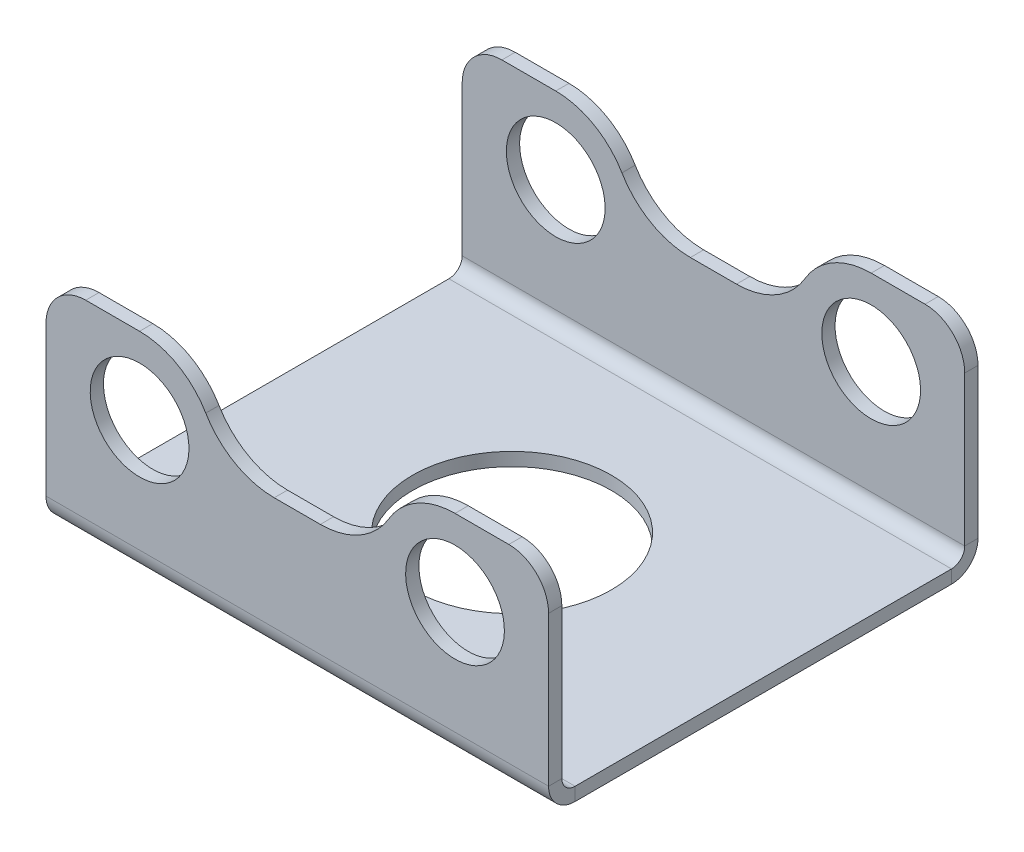
SolidWorks part; units mm, degrees
note: The reader was unsure of these and kept them because the rebuilt part matched: flange length of "Edge-Flange1".
material "Brass"
ref_plane "Front Plane" through (0, 0, 0) normal (0, 0, 1) x (1, 0, 0)
ref_plane "Top Plane" through (0, 0, 0) normal (0, 1, 0) x (1, 0, 0)
ref_plane "Right Plane" through (0, 0, 0) normal (1, 0, 0) x (0, 0, -1)
sketch "Sketch1" plane through (0, 0, 0) normal (0, 1, 0) x (1, 0, 0)
  line L0 (-24.0792, 18.034) -> (24.0792, 18.034)
  line L1 (24.0792, 18.034) -> (24.0792, -18.034)
  line L2 (24.0792, -18.034) -> (-24.0792, -18.034)
  line L3 (-24.0792, -18.034) -> (-24.0792, 18.034)
  line L4 (-24.0792, -18.034) -> (24.0792, 18.034) construction
  circle A0 centre (0, 0) radius 9.525
  point P5 (0, 0)
  dimension "D3" = 19.05
  dimension "D1" = 36.068
  dimension "D2" = 48.1584
base flange "Base-Flange1" sketch "Sketch1" thickness 1.27 reverse thickness direction no parameters "D1"=1.27
edge flange "Edge-Flange1" sketch "Sketch10" flange angle 90 flange length 22.3012 flange position bend outside bend radius 1.27 thickness 1.27 relief rectangular parameters "D6"=10
sketch "Sketch10" plane through (0, 0, -18.034) normal (0, 0, -1) x (-1, 0, 0)
  line L0 (-24.0792, 0) -> (24.0792, 0) construction
  line L1 (-24.0792, 0) -> (24.0792, 0)
  line L2 (-24.0792, 0) -> (-24.0792, 21.0312)
  line L3 (-24.0792, 21.0312) -> (24.0792, 21.0312)
  line L4 (24.0792, 21.0312) -> (24.0792, 0)
  line L5 (-24.0792, -1.27) -> (24.0792, -1.27) construction
  line L6 (15.113, 12.065) -> (-15.113, 12.065) construction
  circle A0 centre (-15.113, 12.065) radius 4.7308
  circle A1 centre (15.113, 12.065) radius 4.7308
  dimension "D2" = 8.9662
  dimension "D3" = 9.4615
  dimension "D1" = 13.335
  dimension "D4" = 30.226
  dimension "D5" = 8.9662
  dimension "D6" = 8.9662
  dimension "D7" = 8.9662
bend "EdgeBend1" bend radius 1.27 bend angle 90 parameters "D5"=1
mirror "Mirror1" about plane through (0, 0, 0) normal (0, 0, 1) of "Edge-Flange1"
bend "MirrorBend1" bend radius 1.27 bend angle 90 parameters "D5"=2
sketch "Sketch11" plane through (0, 0, -20.574) normal (0, 0, -1) x (-1, 0, 0)
  line L2 (24.0792, 21.0312) -> (-24.0792, 21.0312)
  line L5 (7.747, 12.065) -> (-7.747, 12.065)
  line L12 (-15.113, 19.431) -> (-24.0792, 19.431)
  line L13 (-24.0792, 21.0312) -> (-24.0792, 1.27) construction
  line L14 (-24.0792, 19.431) -> (-24.0792, 21.0312)
  line L15 (15.113, 19.431) -> (24.0792, 19.431)
  line L16 (24.0792, 1.27) -> (24.0792, 21.0312) construction
  line L17 (24.0792, 19.431) -> (24.0792, 21.0312)
  circle A2 centre (15.113, 12.065) radius 7.366
  circle A3 centre (-15.113, 12.065) radius 7.366
  dimension "D1" = 14.732
extrude "Cut-Extrude7" cut sketch "Sketch11" against normal through all
fillet "Fillet2" radius 7.62 4 edges at (7.747, 12.065, -19.939) (-7.747, 12.065, -19.939) (-7.747, 12.065, 19.939) (7.747, 12.065, 19.939)
fillet "Fillet3" radius 3.81 4 edges at (24.0792, 19.431, 19.939) (-24.0792, 19.431, 19.939) (-24.0792, 19.431, -19.939) (24.0792, 19.431, -19.939)
sketch "Bend-Lines1" [suppressed] plane through (0, 0, 0) normal (0, 1, 0) x (1, 0, 0)
sketch "Bounding-Box1" [suppressed] plane through (0, 0, 0) normal (0, 1, 0) x (1, 0, 0)
sheet metal parameters "Sheet-Metal1" thickness 1.27 parameters "D1"=1.27
flat pattern "Flat-Pattern1" [suppressed]
sketch "Bend-Lines2" plane through (0, 0, 0) normal (0, 1, 0) x (1, 0, 0)
sketch3d "Bounding-Box2" [suppressed]
  line L0 (-23.495, 18.034, 0) -> (23.495, 18.034, 0) construction
  line L1 (-23.495, -18.034, 0) -> (23.495, -18.034, 0) construction
  line L2 (-23.495, 18.034, 0) -> (-23.495, -18.034, 0) construction
  line L3 (23.495, 18.034, 0) -> (23.495, -18.034, 0) construction
sheet metal parameters "Sheet-Metal2" thickness 1.27 parameters "D1"=1.27
flat pattern "Flat-Pattern1"
sketch "Bend-Lines2" plane through (0, 0, 0) normal (0, 1, 0) x (1, 0, 0)
  line L0 (23.495, 18.2602) -> (-23.495, 18.2602) construction
  line L1 (23.495, 18.2602) -> (-23.495, 18.2602) construction
sketch3d "Bounding-Box2" [suppressed]
  line L0 (-23.495, -18.034, 0) -> (-23.495, 45.4104, 0) construction
  line L1 (23.495, -18.034, 0) -> (23.495, 45.4104, 0) construction
  line L2 (-23.495, -18.034, 0) -> (23.495, -18.034, 0) construction
  line L3 (-23.495, 45.4104, 0) -> (23.495, 45.4104, 0) construction
bend of the flat pattern "Flatten-<EdgeBend1>1"
sheet metal parameters "Sheet-Metal3" thickness 1.27 parameters "D1"=1.27
flat pattern "Flat-Pattern1" [suppressed]
sketch "Bend-Lines2" plane through (0, 0, 0) normal (0, 1, 0) x (1, 0, 0)
  line L0 (24.0792, 19.5302) -> (-24.0792, 19.5302) construction
  line L1 (24.0792, 19.5302) -> (-24.0792, 19.5302) construction
  line L2 (-24.0792, -19.5302) -> (24.0792, -19.5302) construction
  line L3 (-24.0792, -19.5302) -> (24.0792, -19.5302) construction
sketch3d "Bounding-Box2" [suppressed]
  line L0 (-24.0792, -52.8526, 0) -> (-24.0792, 52.8526, 0) construction
  line L1 (24.0792, -52.8526, 0) -> (24.0792, 52.8526, 0) construction
  line L2 (-24.0792, -52.8526, 0) -> (24.0792, -52.8526, 0) construction
  line L3 (-24.0792, 52.8526, 0) -> (24.0792, 52.8526, 0) construction
bend of the flat pattern "Flatten-<EdgeBend1>1"
bend of the flat pattern "Flatten-<MirrorBend1>1"
sketch "Sketch11-1" plane through (0, -1.27, -19.7564) normal (0, -1, 0) x (-1, 0, 0)
  line L2 (24.0792, 24.13) -> (-24.0792, 24.13)
  line L4 (24.0663, 15.1638) -> (25.4769, 15.1638)
  line L5 (7.747, 15.1638) -> (-7.747, 15.1638)
  line L6 (25.4769, 15.1638) -> (25.4769, 24.13)
  line L7 (25.4769, 24.13) -> (24.0792, 24.13)
  line L8 (-24.0663, 15.1638) -> (-25.6537, 15.1638)
  line L9 (-25.6537, 15.1638) -> (-25.6537, 24.13)
  line L10 (-25.6537, 24.13) -> (-24.0792, 24.13)
  line L12 (24.0792, 1.27) -> (-24.0792, 1.27) construction
  circle A2 centre (15.113, 15.1638) radius 7.366
  circle A3 centre (-15.113, 15.1638) radius 7.366
  arc A4 (-15.113, 22.5298) -> (-24.0663, 15.1638) centre (-15.9067, 14.3701) ccw
  arc A5 (15.113, 22.5298) -> (24.0663, 15.1638) centre (15.9067, 14.3701) cw
  dimension "D1" = 14.732
  dimension "D3" = 8.1982
  dimension "D2" = 13.1001
sheet metal parameters "Sheet-Metal11" thickness 1.27 parameters "D1"=1.27
flat pattern "Flat-Pattern1"
sketch "Bend-Lines2" plane through (0, 0, -20.574) normal (0, 0, -1) x (-1, 0, 0)
  line L0 (24.0792, -0.2262) -> (-24.0792, -0.2262) construction
  line L1 (24.0792, -0.2262) -> (-24.0792, -0.2262) construction
  line L2 (24.0792, -39.2866) -> (-24.0792, -39.2866) construction
  line L3 (24.0792, -39.2866) -> (-24.0792, -39.2866) construction
sketch3d "Bounding-Box2" [suppressed]
  line L0 (-24.0793, 19.4309, 0) -> (-24.0792, -58.9437, 0) construction
  line L1 (24.0791, 19.431, 0) -> (24.0792, -58.9437, 0) construction
  line L2 (-24.0793, 19.4309, 0) -> (24.0791, 19.431, 0) construction
  line L3 (-24.0792, -58.9437, 0) -> (24.0792, -58.9437, 0) construction
bend of the flat pattern "Flatten-<MirrorBend1>1"
bend of the flat pattern "Flatten-<EdgeBend1>1"
